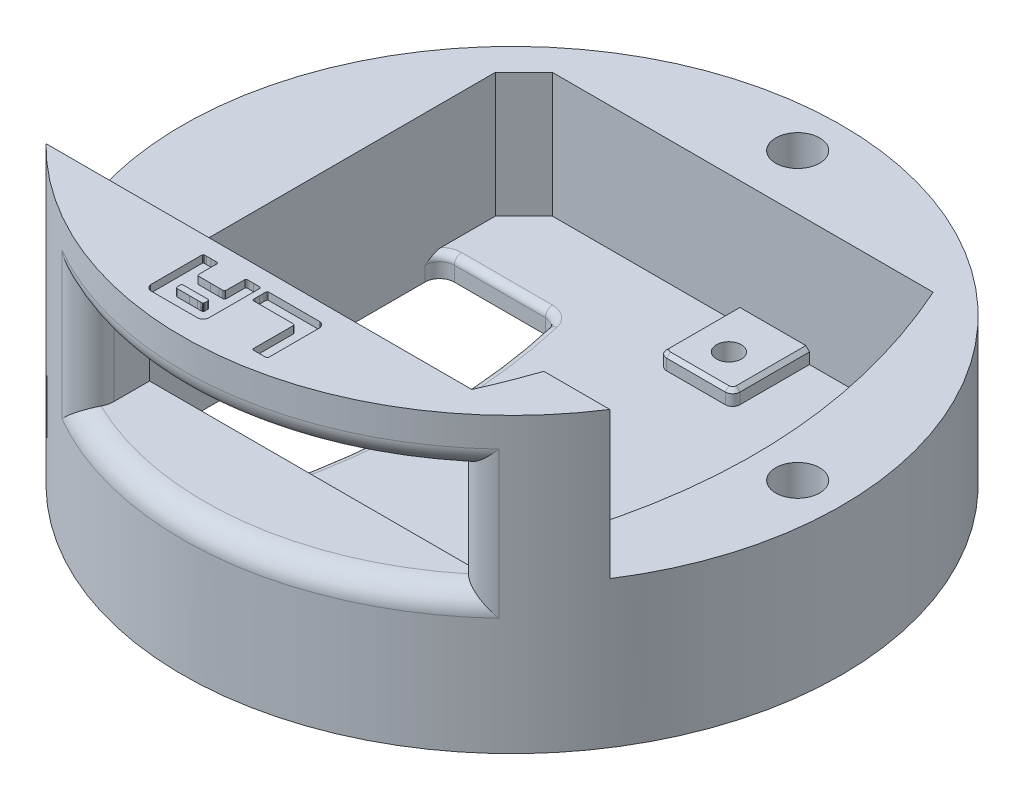
SolidWorks part; units mm, degrees
ref_plane "Plan de face" through (0, 0, 0) normal (0, 0, 1) x (1, 0, 0)
ref_plane "Plan de dessus" through (0, 0, 0) normal (0, 1, 0) x (1, 0, 0)
ref_plane "Plan de droite" through (0, 0, 0) normal (1, 0, 0) x (0, 0, -1)
sketch "Esquisse1" plane through (0, 0, 0) normal (0, 1, 0) x (1, 0, 0)
  circle A0 centre (0, 0) radius 45
  dimension "D1" = 90
extrude "Boss.-Extru.1" add sketch "Esquisse1" along normal blind 40
sketch "Esquisse2" plane through (0, 40, 0) normal (0, 1, 0) x (1, 0, 0)
  line L0 (-26, 31.5) -> (26, 31.5)
  line L1 (26, 0) -> (33, 0) construction
  line L2 (26, 31.5) -> (26, -31.5) construction
  line L3 (-26, 31.5) -> (-29.8891, 27.6109)
  line L4 (-29.8891, 27.6109) -> (-29.8891, 21.6109)
  line L5 (-29.8891, 21.6109) -> (-39.4711, 21.6109)
  line L6 (26, 0) -> (-63.3285, 0) construction
  line L7 (26, 31.5) -> (32.1364, 31.5) construction
  line L8 (-26, 31.5) -> (-32.1364, 31.5) construction
  line L9 (-29.8891, -21.6109) -> (-39.4711, -21.6109)
  line L10 (-29.8891, -27.6109) -> (-29.8891, -21.6109)
  line L11 (-26, -31.5) -> (-29.8891, -27.6109)
  line L12 (-26, -31.5) -> (26, -31.5)
  circle A0 centre (0, 0) radius 45 construction
  arc A1 (-39.4711, -21.6109) -> (-39.4711, 21.6109) centre (0, 0) cw
  spline S0 degree 2 poles (26, 31.5) (40, 0) (26, -31.5) knots 0 0 0 1 1 1
  circle M11 centre (0, 0) radius 45
  dimension "D1" = 52
  dimension "D2" = 7
  dimension "D3" = 63
  dimension "D4" = 135
  dimension "D5" = 5.5
  dimension "D6" = 6
extrude "Enlèv. mat.-Extru.1" cut sketch "Esquisse2" against normal offset from surface (37 mm away) 3 contours S0 L0 L3 L4 L5 L9 L10 L11 L12 M11 region at (-4.3513, 40, 0) up to face at (0, 0, 45)
sketch "Esquisse7" plane through (0, 3, 0) normal (0, 1, 0) x (1, 0, 0)
  line L0 (9.1109, 30) -> (-0.8891, 21) construction
  line L1 (9.1109, 30) -> (9.1109, 22)
  line L2 (8.1109, 21) -> (0.1109, 21)
  line L3 (-0.8891, 30) -> (-0.8891, 22)
  line L4 (-0.8891, 30) -> (9.1109, 30) construction
  line L5 (-0.8891, 30) -> (-0.8891, 31.5)
  line L6 (-0.8891, 31.5) -> (9.1109, 31.5)
  line L7 (9.1109, 30) -> (9.1109, 31.5)
  line L8 (-34.6801, 0) -> (18.839, 0) construction
  line L9 (9.1109, -30) -> (-0.8891, -21) construction
  line L10 (9.1109, -30) -> (9.1109, -31.5)
  line L11 (-0.8891, -31.5) -> (9.1109, -31.5)
  line L12 (-0.8891, -30) -> (-0.8891, -31.5)
  line L13 (-0.8891, -30) -> (-0.8891, -22)
  line L14 (8.1109, -21) -> (0.1109, -21)
  line L15 (9.1109, -30) -> (9.1109, -22)
  line L16 (-34.6801, 21.6109) -> (-34.6801, -21.6109) construction
  line L17 (-26, 31.5) -> (26, 31.5) construction
  line L18 (-29.8891, 21.6109) -> (-39.4711, 21.6109) construction
  arc A0 (0.1109, 21) -> (-0.8891, 22) centre (0.1109, 22) cw
  arc A1 (9.1109, 22) -> (8.1109, 21) centre (8.1109, 22) cw
  arc A2 (9.1109, -22) -> (8.1109, -21) centre (8.1109, -22) ccw
  arc A3 (0.1109, -21) -> (-0.8891, -22) centre (0.1109, -22) ccw
  point P26 (-34.6801, 0)
  point P35 (-34.6801, 21.6109)
  dimension "D2" = 1
  dimension "D1" = 10
  dimension "D3" = 8
  dimension "D4" = 1.5
  dimension "D5" = 33.791
extrude "Boss.-Extru.4" add sketch "Esquisse7" along normal blind 2
chamfer "Chanfrein4" distance 0.5 angle 45 10 edges at (-0.8891, 5, -26.75) (9.1109, 5, -26.75) (-0.5962, 5, -21.2929) (8.818, 5, -21.2929) (4.1109, 5, -21) (9.1109, 5, 26.75) (-0.8891, 5, 26.75) (8.818, 5, 21.2929) (-0.5962, 5, 21.2929) (4.1109, 5, 21)
sketch "Esquisse8" plane through (0, 0, 0) normal (0, -1, 0) x (1, 0, 0)
  line L0 (8.1109, 21.5) -> (0.1109, 21.5) construction
  line L1 (4.1109, 25.5) -> (4.1109, 21.5) construction
  line L2 (0, 0) -> (-4.4948, 0) construction
  circle A0 centre (4.1109, 25.5) radius 1.7
  circle A1 centre (4.1109, -25.5) radius 1.7
  dimension "D1" = 3.4
  dimension "D2" = 4
extrude "Enlèv. mat.-Extru.4" cut sketch "Esquisse8" against normal up to next
chamfer "Chanfrein5" distance 1.5 angle 45 2 edges at (4.1109, 0, -23.8) (4.1109, 0, 23.8)
sketch "Esquisse9" plane through (0, 0, 31.5) normal (0, 0, -1) x (-1, 0, 0)
  line L0 (-26, 33) -> (18, 33)
  line L1 (-26, 33) -> (-26, 19)
  line L2 (-26, 19) -> (18, 19)
  line L3 (18, 33) -> (18, 19)
  line L4 (0.8891, 3) -> (26, 3) construction
  line L5 (-26, 3) -> (-26, 40) construction
  dimension "D1" = 44
  dimension "D2" = 14
  dimension "D3" = 30
extrude "Enlèv. mat.-Extru.5" cut sketch "Esquisse9" against normal up to next
fillet "Congé1" radius 3 4 edges at (26, 26, 36.7287) (4.5929, 33, 44.765) (-18, 26, 41.2432) (4.5929, 19, 44.765)
sketch "Esquisse10" plane through (0, 40, 0) normal (0, 1, 0) x (1, 0, 0)
  line L0 (28.7878, -24.4353) -> (37.7878, -24.4353)
  line L1 (-26, -31.5) -> (-32.1364, -31.5)
  line L2 (-26, -31.5) -> (28.7878, -24.4353)
  arc A0 (-39.4711, -21.6109) -> (-39.4711, 21.6109) centre (0, 0) ccw construction
  arc A1 (-32.1364, -31.5) -> (37.7878, -24.4353) centre (0, 0) cw
  parabola Q5 (26, 31.5) -> (26, -31.5) focus (-2.4375, 0) apex (33, 0) construction
  dimension "D1" = 9
extrude "Enlèv. mat.-Extru.6" cut sketch "Esquisse10" against normal offset from surface (20 mm away) 20 up to face at (4.1109, 0, -22.3)
sketch "Esquisse11" plane through (0, 20, 0) normal (0, 1, 0) x (1, 0, 0)
  line L0 (0, 0) -> (0, 45) construction
  line L1 (0, 0) -> (45, 0) construction
  circle A0 centre (0, 39) radius 1.6
  circle A1 centre (39, 0) radius 1.6
  arc A2 (37.7878, -24.4353) -> (-39.4711, 21.6109) centre (0, 0) ccw construction
  dimension "D1" = 3.2
  dimension "D2" = 3.2
  dimension "D3" = 6
  dimension "D4" = 6
extrude "Enlèv. mat.-Extru.7" cut sketch "Esquisse11" against normal through all
sketch "Esquisse12" plane through (0, 20, 0) normal (0, 1, 0) x (1, 0, 0)
  circle A0 centre (0, 39) radius 3
  circle A1 centre (39, 0) radius 3
  dimension "D1" = 6
  dimension "D2" = 6
extrude "Enlèv. mat.-Extru.8" cut sketch "Esquisse12" against normal blind 10
sketch "Esquisse13" plane through (0, 3, 0) normal (0, 1, 0) x (1, 0, 0)
  line L0 (-29.8891, 21.6109) -> (-29.8891, -21.6109)
  line L1 (-29.8891, -21.6109) -> (-39.4711, -21.6109)
  line L2 (-39.4711, -21.6109) -> (-39.4711, 21.6109) construction
  line L3 (-39.4711, 21.6109) -> (-29.8891, 21.6109)
  arc A0 (-39.4711, 21.6109) -> (-39.4711, -21.6109) centre (0, 0) ccw
extrude "Enlèv. mat.-Extru.9" cut sketch "Esquisse13" against normal up to next
sketch "Esquisse14" plane through (0, 40, 0) normal (0, 1, 0) x (1, 0, 0)
  line L0 (8.3336, -41.5636) -> (8.3347, -40.5342)
  line L1 (8.3343, -38.0353) -> (8.3304, -34.5148)
  line L2 (8.3304, -34.5148) -> (8.3008, -34.4281)
  line L3 (7.7437, -33.8777) -> (7.6504, -33.8481)
  line L4 (7.6504, -33.8481) -> (4.1022, -33.8481)
  line L5 (4.1022, -33.8481) -> (0.5541, -33.8481)
  line L6 (0.5541, -33.8481) -> (0.5063, -33.8845)
  line L7 (0.5227, -35.8917) -> (0.5668, -35.9217)
  line L8 (0.5668, -35.9217) -> (3.3223, -35.9217)
  line L9 (3.3223, -35.9217) -> (6.0778, -35.9217)
  line L10 (6.0778, -35.9217) -> (6.1373, -35.9517)
  line L11 (6.2268, -36.0412) -> (6.2569, -36.1007)
  line L12 (6.2569, -36.1007) -> (6.2569, -38.8562)
  line L13 (6.2569, -38.8562) -> (6.2569, -41.6118)
  line L14 (6.2569, -41.6118) -> (6.2869, -41.6559)
  line L15 (-0.5008, -33.8845) -> (-0.5486, -33.8481)
  line L16 (-0.5486, -33.8481) -> (-1.4297, -33.8443)
  line L17 (-2.4541, -33.9258) -> (-2.4842, -33.9681)
  line L18 (-2.4842, -33.9681) -> (-2.4909, -35.2883)
  line L19 (-2.4909, -35.2883) -> (-2.4976, -36.6084)
  line L20 (-2.4976, -36.6084) -> (-2.5281, -36.6575)
  line L21 (-4.3923, -36.7586) -> (-6.1114, -36.7551)
  line L22 (-6.1114, -36.7551) -> (-6.1563, -36.7231)
  line L23 (-6.2511, -35.2869) -> (-6.2514, -33.992)
  line L24 (-6.2514, -33.992) -> (-6.2814, -33.948)
  line L25 (-8.2975, -33.9399) -> (-8.325, -33.9767)
  line L26 (-8.325, -33.9767) -> (-8.325, -37.5262)
  line L27 (-8.325, -37.5262) -> (-8.325, -41.0756)
  line L28 (-8.325, -41.0756) -> (-8.2954, -41.169)
  line L29 (-7.7449, -41.7261) -> (-7.6582, -41.7557)
  line L30 (-7.6582, -41.7557) -> (-4.4045, -41.7581)
  line L31 (-6.1563, -38.8807) -> (-6.1114, -38.8487)
  line L32 (-6.1114, -38.8487) -> (-4.3923, -38.8452)
  line L33 (-4.3717, -39.6821) -> (-6.0724, -39.6821)
  line L34 (-6.0724, -39.6821) -> (-6.1319, -39.6521)
  arc A0 (8.2111, -41.7438) -> (8.2503, -41.7196) centre (8.1444, -41.5919) ccw
  arc A1 (8.2503, -41.7196) -> (8.2873, -41.6824) centre (8.0739, -41.507) ccw
  arc A2 (8.2873, -41.6824) -> (8.3161, -41.6396) centre (8.08, -41.5119) ccw
  arc A3 (8.3161, -41.6396) -> (8.3304, -41.5987) centre (8.1957, -41.5745) ccw
  arc A4 (8.3304, -41.5987) -> (8.3336, -41.5636) centre (8.1333, -41.5633) ccw
  arc A5 (8.3347, -40.5342) -> (8.3352, -39.3881) centre (-841.87, -39.6126) ccw
  arc A6 (8.3352, -39.3881) -> (8.3343, -38.0353) centre (-1633.4732, -39.822) ccw
  arc A7 (8.3008, -34.4281) -> (8.2131, -34.2445) centre (7.4674, -34.7132) ccw
  arc A8 (8.2131, -34.2445) -> (8.0855, -34.0854) centre (7.4612, -34.7171) ccw
  arc A9 (8.0855, -34.0854) -> (7.9258, -33.9606) centre (7.4691, -34.7091) ccw
  arc A10 (7.9258, -33.9606) -> (7.7437, -33.8777) centre (7.4923, -34.6712) ccw
  arc A11 (0.5063, -33.8845) -> (0.4515, -33.9549) centre (0.6125, -34.0238) ccw
  arc A12 (0.4515, -33.9549) -> (0.426, -34.0571) centre (0.7557, -34.0851) ccw
  arc A13 (0.426, -34.0571) -> (0.4175, -34.2554) centre (2.7542, -34.2551) ccw
  arc A14 (0.4175, -34.2554) -> (0.419, -34.9106) centre (156.8501, -34.2344) ccw
  arc A15 (0.419, -34.9106) -> (0.422, -35.4849) centre (327.504, -33.4972) ccw
  arc A16 (0.422, -35.4849) -> (0.4259, -35.6777) centre (7.164, -35.444) ccw
  arc A17 (0.4259, -35.6777) -> (0.4331, -35.7791) centre (1.8243, -35.6292) ccw
  arc A18 (0.4331, -35.7791) -> (0.4507, -35.824) centre (0.5246, -35.7693) ccw
  arc A19 (0.4507, -35.824) -> (0.4645, -35.8406) centre (0.6004, -35.713) ccw
  arc A20 (0.4645, -35.8406) -> (0.4833, -35.8594) centre (0.774, -35.5501) ccw
  arc A21 (0.4833, -35.8594) -> (0.5038, -35.8774) centre (0.7829, -35.5406) ccw
  arc A22 (0.5038, -35.8774) -> (0.5227, -35.8917) centre (0.6636, -35.6845) ccw
  arc A23 (6.1669, -35.9691) -> (6.1373, -35.9517) centre (6.0187, -36.1869) ccw
  arc A24 (6.1902, -35.9883) -> (6.1669, -35.9691) centre (6.0763, -36.1022) ccw
  arc A25 (6.2095, -36.0117) -> (6.1902, -35.9883) centre (6.0763, -36.1022) ccw
  arc A26 (6.2268, -36.0412) -> (6.2095, -36.0117) centre (5.9916, -36.1598) ccw
  arc A27 (6.2869, -41.6559) -> (6.3011, -41.6748) centre (6.494, -41.5149) ccw
  arc A28 (6.3011, -41.6748) -> (6.3191, -41.6952) centre (6.6379, -41.3956) ccw
  arc A29 (6.3191, -41.6952) -> (6.3379, -41.714) centre (6.6283, -41.4046) ccw
  arc A30 (6.3379, -41.714) -> (6.3545, -41.7278) centre (6.4655, -41.5781) ccw
  arc A31 (6.3545, -41.7278) -> (6.3996, -41.7454) centre (6.4092, -41.654) ccw
  arc A32 (6.3996, -41.7454) -> (6.5022, -41.7525) centre (6.55, -40.319) ccw
  arc A33 (6.5022, -41.7525) -> (6.6973, -41.7562) centre (6.7322, -34.8454) ccw
  arc A34 (6.6973, -41.7562) -> (7.2813, -41.7587) centre (8.4138, 298.5438) ccw
  arc A35 (7.2813, -41.7587) -> (7.7496, -41.7595) centre (7.7994, 113.931) ccw
  arc A36 (7.7496, -41.7595) -> (8.0034, -41.7576) centre (7.7546, -26.229) ccw
  arc A37 (8.0034, -41.7576) -> (8.1674, -41.7537) centre (7.8312, -31.0139) ccw
  arc A38 (8.1674, -41.7537) -> (8.2111, -41.7438) centre (8.1637, -41.636) ccw
  arc A39 (-1.068, -41.7424) -> (-0.9412, -41.7017) centre (-1.217, -41.0597) ccw
  arc A40 (-0.9412, -41.7017) -> (-0.8145, -41.6353) centre (-1.3068, -40.8508) ccw
  arc A41 (-0.8145, -41.6353) -> (-0.698, -41.5491) centre (-1.3195, -40.8305) ccw
  arc A42 (-0.698, -41.5491) -> (-0.6013, -41.4495) centre (-1.2221, -40.9431) ccw
  arc A43 (-0.6013, -41.4495) -> (-0.5559, -41.3871) centre (-1.1275, -41.0203) ccw
  arc A44 (-0.5559, -41.3871) -> (-0.5127, -41.3131) centre (-1.4204, -40.8323) ccw
  arc A45 (-0.5127, -41.3131) -> (-0.474, -41.2323) centre (-1.4999, -40.7902) ccw
  arc A46 (-0.474, -41.2323) -> (-0.4421, -41.149) centre (-1.4788, -40.7993) ccw
  arc A47 (-0.4421, -41.149) -> (-0.4255, -41.0529) centre (-0.7411, -41.0481) ccw
  arc A48 (-0.4255, -41.0529) -> (-0.4202, -40.5962) centre (-62.4465, -40.1056) ccw
  arc A49 (-0.4202, -40.5962) -> (-0.4165, -39.7961) centre (-125.2051, -39.6091) ccw
  arc A50 (-0.4165, -39.7961) -> (-0.4136, -37.5552) centre (-4958.0687, -32.364) ccw
  arc A51 (-0.4136, -37.5552) -> (-0.4116, -34.8688) centre (-4418.828, -32.926) ccw
  arc A52 (-0.4116, -34.8688) -> (-0.4185, -34.2772) centre (-24.8776, -34.8581) ccw
  arc A53 (-0.4185, -34.2772) -> (-0.4388, -33.993) centre (-3.4147, -34.3483) ccw
  arc A54 (-0.4388, -33.993) -> (-0.5008, -33.8845) centre (-0.5981, -34.0121) ccw
  arc A55 (-1.4297, -33.8443) -> (-2.0823, -33.8429) centre (-2.098, -191.4752) ccw
  arc A56 (-2.0823, -33.8429) -> (-2.2852, -33.851) centre (-2.0826, -36.3993) ccw
  arc A57 (-2.2852, -33.851) -> (-2.3884, -33.8747) centre (-2.2564, -34.2128) ccw
  arc A58 (-2.3884, -33.8747) -> (-2.4541, -33.9258) centre (-2.3355, -34.0104) ccw
  arc A59 (-2.5443, -36.6791) -> (-2.5281, -36.6575) centre (-2.6594, -36.5758) ccw
  arc A60 (-2.5661, -36.7006) -> (-2.5443, -36.6791) centre (-2.7327, -36.51) ccw
  arc A61 (-2.5908, -36.7197) -> (-2.5661, -36.7006) centre (-2.739, -36.5028) ccw
  arc A62 (-2.6159, -36.7343) -> (-2.5908, -36.7197) centre (-2.7012, -36.5581) ccw
  arc A63 (-2.687, -36.7523) -> (-2.6159, -36.7343) centre (-2.6954, -36.5701) ccw
  arc A64 (-2.8814, -36.7582) -> (-2.687, -36.7523) centre (-2.9632, -30.7765) ccw
  arc A65 (-3.2474, -36.7604) -> (-2.8814, -36.7582) centre (-3.2177, -12.1526) ccw
  arc A66 (-4.3923, -36.7586) -> (-3.2474, -36.7604) centre (-1.564, 1359.5283) ccw
  arc A67 (-6.1753, -36.7069) -> (-6.1563, -36.7231) centre (-6.0726, -36.6058) ccw
  arc A68 (-6.1952, -36.6844) -> (-6.1753, -36.7069) centre (-5.9615, -36.4964) ccw
  arc A69 (-6.2132, -36.6597) -> (-6.1952, -36.6844) centre (-5.9561, -36.492) ccw
  arc A70 (-6.226, -36.6364) -> (-6.2132, -36.6597) centre (-6.0662, -36.5639) ccw
  arc A71 (-6.2414, -36.5728) -> (-6.226, -36.6364) centre (-6.0662, -36.5639) ccw
  arc A72 (-6.2473, -36.4048) -> (-6.2414, -36.5728) centre (-1.0597, -36.3083) ccw
  arc A73 (-6.2504, -36.1005) -> (-6.2473, -36.4048) centre (11.5933, -36.0728) ccw
  arc A74 (-6.2511, -35.2869) -> (-6.2504, -36.1005) centre (606.421, -35.1486) ccw
  arc A75 (-6.2814, -33.948) -> (-6.2956, -33.929) centre (-6.4884, -34.0888) ccw
  arc A76 (-6.2956, -33.929) -> (-6.3136, -33.9086) centre (-6.6323, -34.2081) ccw
  arc A77 (-6.3136, -33.9086) -> (-6.3324, -33.8898) centre (-6.6228, -34.1992) ccw
  arc A78 (-6.3324, -33.8898) -> (-6.349, -33.876) centre (-6.46, -34.0257) ccw
  arc A79 (-6.349, -33.876) -> (-6.3943, -33.8584) centre (-6.4036, -33.9496) ccw
  arc A80 (-6.3943, -33.8584) -> (-6.4978, -33.8517) centre (-6.5407, -35.2993) ccw
  arc A81 (-6.4978, -33.8517) -> (-6.695, -33.8486) centre (-6.7067, -40.9083) ccw
  arc A82 (-6.695, -33.8486) -> (-7.2915, -33.8481) centre (-7.2912, -393.2007) ccw
  arc A83 (-7.2915, -33.8481) -> (-7.8847, -33.8486) centre (-7.2913, -386.0898) ccw
  arc A84 (-7.8847, -33.8486) -> (-8.0836, -33.8516) centre (-7.8725, -41.0822) ccw
  arc A85 (-8.0836, -33.8516) -> (-8.1885, -33.8583) centre (-8.0385, -35.3954) ccw
  arc A86 (-8.1885, -33.8583) -> (-8.2332, -33.8756) centre (-8.1799, -33.947) ccw
  arc A87 (-8.2332, -33.8756) -> (-8.2493, -33.8888) centre (-8.0952, -34.0603) ccw
  arc A88 (-8.2493, -33.8888) -> (-8.2672, -33.9058) centre (-7.9414, -34.2316) ccw
  arc A89 (-8.2672, -33.9058) -> (-8.2843, -33.9238) centre (-7.9414, -34.2316) ccw
  arc A90 (-8.2843, -33.9238) -> (-8.2975, -33.9399) centre (-8.1127, -34.0778) ccw
  arc A91 (-8.2954, -41.169) -> (-8.2124, -41.3515) centre (-7.4953, -40.9155) ccw
  arc A92 (-8.2124, -41.3515) -> (-8.0879, -41.511) centre (-7.4692, -40.8996) ccw
  arc A93 (-8.0879, -41.511) -> (-7.929, -41.6383) centre (-7.4611, -40.8916) ccw
  arc A94 (-7.929, -41.6383) -> (-7.7449, -41.7261) centre (-7.4574, -40.8858) ccw
  arc A95 (-4.4045, -41.7581) -> (-2.6497, -41.7587) centre (-2.7092, 2304.2614) ccw
  arc A96 (-2.6497, -41.7587) -> (-1.7515, -41.7566) centre (-2.6547, 149.9899) ccw
  arc A97 (-1.7515, -41.7566) -> (-1.1629, -41.753) centre (-2.7432, 168.7567) ccw
  arc A98 (-1.1629, -41.753) -> (-1.068, -41.7424) centre (-1.1664, -41.2915) ccw
  arc A99 (-6.1614, -39.6348) -> (-6.1319, -39.6521) centre (-6.0133, -39.4169) ccw
  arc A100 (-6.1847, -39.6155) -> (-6.1614, -39.6348) centre (-6.0709, -39.5016) ccw
  arc A101 (-6.204, -39.5922) -> (-6.1847, -39.6155) centre (-6.0709, -39.5016) ccw
  arc A102 (-6.2214, -39.5626) -> (-6.204, -39.5922) centre (-5.9862, -39.444) ccw
  arc A103 (-6.2381, -39.5202) -> (-6.2214, -39.5626) centre (-5.9976, -39.4498) ccw
  arc A104 (-6.2468, -39.4756) -> (-6.2381, -39.5202) centre (-6.0036, -39.4515) ccw
  arc A105 (-6.2504, -39.4082) -> (-6.2468, -39.4756) centre (-5.4887, -39.4006) ccw
  arc A106 (-6.2511, -39.2626) -> (-6.2504, -39.4082) centre (6.6941, -39.2784) ccw
  arc A107 (-6.2476, -39.0858) -> (-6.2511, -39.2626) centre (-1.5054, -39.2684) ccw
  arc A108 (-6.2342, -38.9915) -> (-6.2476, -39.0858) centre (-5.7823, -39.1037) ccw
  arc A109 (-6.206, -38.9304) -> (-6.2342, -38.9915) centre (-6.0604, -39.0346) ccw
  arc A110 (-6.1563, -38.8807) -> (-6.206, -38.9304) centre (-6.032, -39.055) ccw
  arc A111 (-3.2474, -38.8434) -> (-4.3923, -38.8452) centre (-1.564, -1435.1321) ccw
  arc A112 (-2.8814, -38.8456) -> (-3.2474, -38.8434) centre (-3.2177, -63.4512) ccw
  arc A113 (-2.687, -38.8515) -> (-2.8814, -38.8456) centre (-2.9632, -44.8273) ccw
  arc A114 (-2.6159, -38.8695) -> (-2.687, -38.8515) centre (-2.6954, -39.0337) ccw
  arc A115 (-2.5908, -38.8841) -> (-2.6159, -38.8695) centre (-2.7012, -39.0457) ccw
  arc A116 (-2.5661, -38.9032) -> (-2.5908, -38.8841) centre (-2.739, -39.101) ccw
  arc A117 (-2.5443, -38.9247) -> (-2.5661, -38.9032) centre (-2.7327, -39.0938) ccw
  arc A118 (-2.5281, -38.9463) -> (-2.5443, -38.9247) centre (-2.6594, -39.028) ccw
  arc A119 (-2.5107, -38.9839) -> (-2.5281, -38.9463) centre (-2.6722, -39.0359) ccw
  arc A120 (-2.5019, -39.0263) -> (-2.5107, -38.9839) centre (-2.7022, -39.0456) ccw
  arc A121 (-2.4983, -39.0952) -> (-2.5019, -39.0263) centre (-3.2845, -39.1019) ccw
  arc A122 (-2.4976, -39.2621) -> (-2.4983, -39.0952) centre (-22.0355, -39.2621) ccw
  arc A123 (-2.4983, -39.4287) -> (-2.4976, -39.2621) centre (-21.9238, -39.2621) ccw
  arc A124 (-2.5019, -39.4977) -> (-2.4983, -39.4287) centre (-3.2907, -39.4219) ccw
  arc A125 (-2.5106, -39.5401) -> (-2.5019, -39.4977) centre (-2.7041, -39.4783) ccw
  arc A126 (-2.5279, -39.5776) -> (-2.5106, -39.5401) centre (-2.6701, -39.4892) ccw
  arc A127 (-2.5438, -39.5987) -> (-2.5279, -39.5776) centre (-2.6545, -39.4988) ccw
  arc A128 (-2.5657, -39.6204) -> (-2.5438, -39.5987) centre (-2.7467, -39.4157) ccw
  arc A129 (-2.5903, -39.6398) -> (-2.5657, -39.6204) centre (-2.7521, -39.4096) ccw
  arc A130 (-2.6146, -39.6542) -> (-2.5903, -39.6398) centre (-2.6965, -39.4887) ccw
  arc A131 (-2.6846, -39.6724) -> (-2.6146, -39.6542) centre (-2.6932, -39.4954) ccw
  arc A132 (-2.8772, -39.6786) -> (-2.6846, -39.6724) centre (-2.9707, -33.7894) ccw
  arc A133 (-3.2396, -39.6816) -> (-2.8772, -39.6786) centre (-3.2599, -15.5832) ccw
  arc A134 (-4.3717, -39.6821) -> (-3.2396, -39.6816) centre (-4.3808, 1320.9145) ccw
extrude "Signature" cut sketch "Esquisse14" against normal blind 1
sketch "Esquisse15" plane through (0, 20, 0) normal (0, 1, 0) x (1, 0, 0)
  line L0 (-39.4711, 21.6109) -> (-29.8891, 21.6109)
  line L1 (-29.8891, 21.6109) -> (-29.8891, -21.6109)
  line L2 (-29.8891, -21.6109) -> (-39.4711, -21.6109)
  arc A0 (-39.4711, -21.6109) -> (-39.4711, 21.6109) centre (0, 0) cw
extrude "Boss.-Extru.5" add sketch "Esquisse15" against normal up to surface (20 mm away) up to face at (0, 0, -37.4)
sketch "Esquisse16" plane through (0, 3, 0) normal (0, 1, 0) x (1, 0, 0)
  line L0 (-29.8891, 20) -> (-13.8891, 20)
  line L1 (-29.8891, -27.6109) -> (-29.8891, 27.6109) construction
  line L2 (-13.8891, 20) -> (-13.8891, -20) construction
  line L3 (-13.8891, -20) -> (-29.8891, -20)
  line L4 (-29.8891, -20) -> (-29.8891, 20)
  line L5 (0, 0) -> (-13.8891, 0) construction
  arc A0 (-13.8891, 20) -> (-13.8891, -20) centre (-93.4127, 0) cw
  dimension "D1" = 16
  dimension "D2" = 82
  dimension "D3" = 40
extrude "Enlèv. mat.-Extru.10" cut sketch "Esquisse16" against normal up to next
fillet "Congé2" radius 2 4 edges at (-13.8891, 1.5, 20) (-29.8891, 1.5, 20) (-29.8891, 1.5, -20) (-13.8891, 1.5, -20)
fillet "Congé3" radius 1 7 edges at (-29.3033, 3, 19.4142) (-21.6765, 3, 20) (-14.219, 3, 19.5652) (-29.3033, 3, -19.4142) (-21.6765, 3, -20) (-14.219, 3, -19.5652) (-11.4127, 3, 0)
sketch "Esquisse17" plane through (0, 0, 0) normal (0, -1, 0) x (1, 0, 0)
  line L0 (-29.8891, 18) -> (-29.8891, -18) construction
  line L1 (-29.8891, 3.5) -> (-51.7101, 3.5)
  line L2 (-29.8891, 3.5) -> (-29.8891, -3.5)
  line L3 (-29.8891, -3.5) -> (-51.7101, -3.5)
  line L4 (-51.7101, 3.5) -> (-51.7101, -3.5)
  line L5 (-29.8891, 0) -> (0, 0) construction
  dimension "D1" = 7
extrude "Enlèv. mat.-Extru.11" cut sketch "Esquisse17" against normal blind 3
fillet "Congé4" radius 1 8 edges at (-29.8891, 1.5, 3.5) (-44.8637, 1.5, -3.5) (-29.8891, 3, 0) (-45, 3, 0) (-29.8891, 1.5, -3.5) (-44.8637, 1.5, 3.5) (-37.3764, 3, 3.5) (-37.3764, 3, -3.5)
